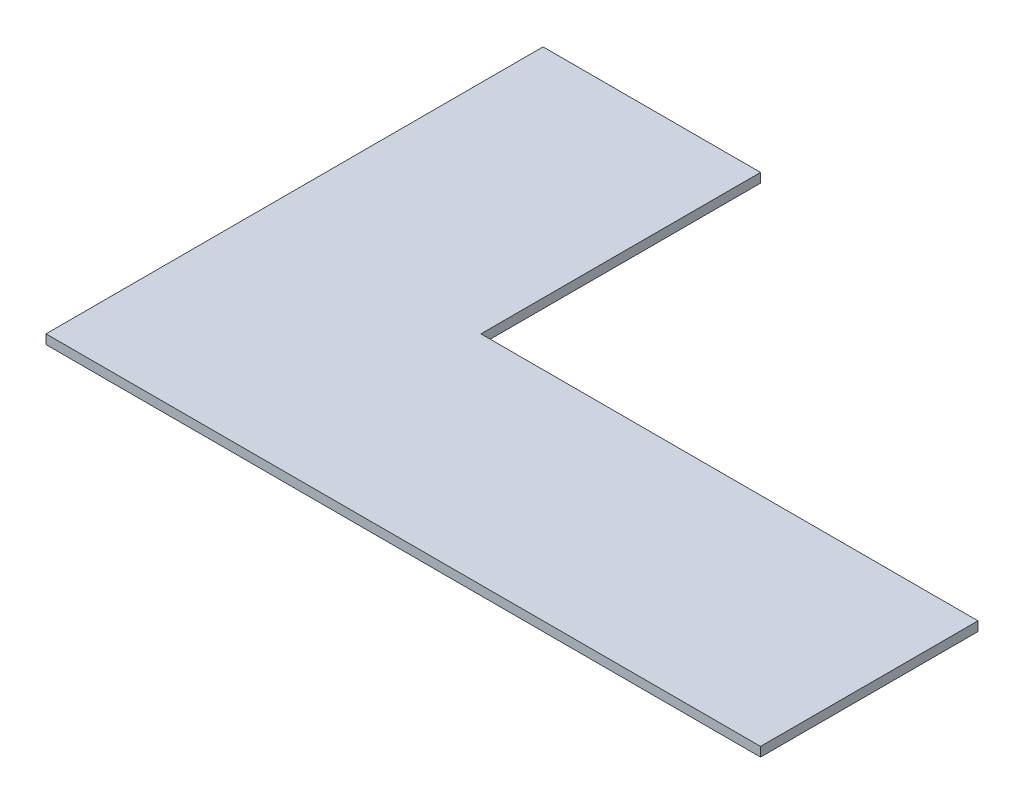
SolidWorks part; units mm, degrees
ref_plane "Front Plane" through (0, 0, 0) normal (0, 0, 1) x (1, 0, 0)
ref_plane "Top Plane" through (0, 0, 0) normal (0, 1, 0) x (1, 0, 0)
ref_plane "Right Plane" through (0, 0, 0) normal (1, 0, 0) x (0, 0, -1)
sketch "Sketch1" plane through (0, 0, 0) normal (0, 1, 0) x (1, 0, 0)
  line L0 (-115, -35) -> (115, -35)
  line L2 (-115, -35) -> (-115, 35)
  line L4 (115, -35) -> (115, 35)
  line L5 (-115, -35) -> (115, 35) construction
  line L6 (-115, 35) -> (115, -35) construction
  line L15 (-45, 35) -> (115, 35)
  line L17 (-115, 35) -> (-115, 125)
  line L18 (-115, 125) -> (-45, 125)
  line L19 (-45, 35) -> (-45, 125)
  point P0 (0, 0)
  dimension "D1" = 230
  dimension "D2" = 70
  dimension "D3" = 70
  dimension "D4" = 160
extrude "Boss-Extrude1" add sketch "Sketch1" along normal blind 3
